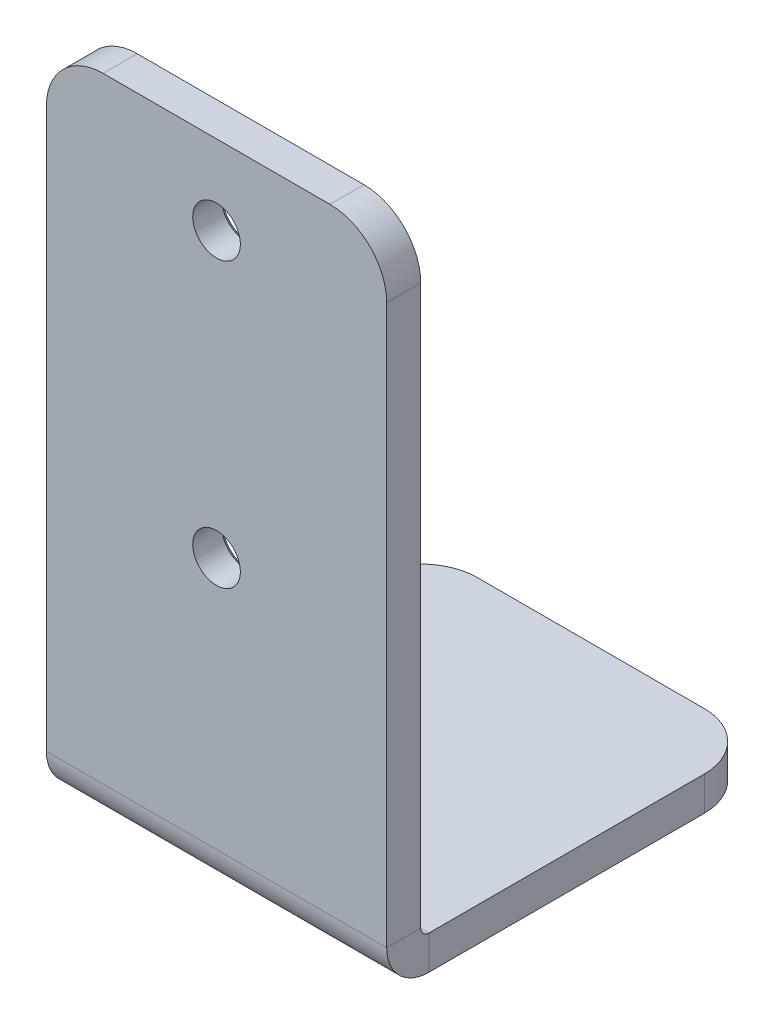
SolidWorks part; units mm, degrees
note: The reader was unsure of these and kept them because the rebuilt part matched: bend radius of "TabanBükümü1".
ref_plane "Ön Düzlem" through (0, 0, 0) normal (0, 0, 1) x (1, 0, 0)
ref_plane "Üst Düzlem" through (0, 0, 0) normal (0, 1, 0) x (1, 0, 0)
ref_plane "Sağ Düzlem" through (0, 0, 0) normal (1, 0, 0) x (0, 0, -1)
sketch "Sketch1" plane through (0, 0, 0) normal (1, 0, 0) x (0, 0, -1)
  line L0 (0, 0) -> (0, -55)
  line L1 (0, -55) -> (30, -55)
  dimension "D1" = 55
  dimension "D2" = 30
base flange "Base-Flange1" sketch "Sketch1" end condition mid plane depth 30 reverse direction no thickness 3 reverse thickness direction no bend radius 0.7366
bend "TabanBükümü1" bend radius 0.7366 bend angle 90 parameters "D5"=1
sketch "Sketch6" plane through (0, 0, 0) normal (0, 0, -1) x (-1, 0, 0)
  line L0 (0, -58) -> (0, -32) construction
  line L1 (-15, -58) -> (15, -58) construction
  line L2 (0, 0) -> (0, -55) construction
  line L3 (0, -32) -> (0, -7) construction
  dimension "D1" = 25
  dimension "D2" = 26
hole_wizard "M5 Tapped Hole1" positions "Sketch7" profile "Sketch8" tap size "M5" standard "ISO"
sketch "Sketch7" plane through (0, 0, 0) normal (0, 0, -1) x (-1, 0, 0)
  point P0 (0, -32)
  point P3 (0, -7)
sketch "Sketch8" plane through (0, -32, 0) normal (1, 0, 0) x (0, 1, 0)
  line L0 (0, 0) -> (0, 15.2618)
  line L1 (0, 15.2618) -> (2.1, 14)
  line L2 (2.1, 14) -> (2.1, 0.425)
  line L3 (2.1, 0.425) -> (2.525, 0)
  line L5 (2.525, 0) -> (0, 0)
  line L6 (-2.1, 0.425) -> (-2.525, 0) construction
  line L10 (0, 15.2618) -> (-2.1, 14) construction
  line L11 (0, -6.35) -> (0, 107.95) construction
  dimension "Tap Drill Dia." = 4.2
  dimension "Tap Drill Depth" = 14
  dimension "Near C'Sink Dia." = 5.05
  dimension "Near C'Sink Angle" = 90
  dimension "Drill Angle" = 118
cosmetic thread "Hole Thread1"
cosmetic thread "Hole Thread2"
fillet "Fillet1" radius 5 4 edges at (-15, -56.5, -30) (15, -56.5, -30) (15, 0, 1.5) (-15, 0, 1.5)
sketch "Büküm-Çizgileri1" [suppressed] plane through (0, 0, 0) normal (0, 1, 0) x (1, 0, 0)
sketch "Sınırlandırma-Kutusu1" [suppressed] plane through (0, 0, 0) normal (0, 1, 0) x (1, 0, 0)
sheet metal parameters "Sac-Levha1" thickness 3 parameters "D1"=0.7366
flat pattern "Düz-Çoğaltma1" [suppressed]
sketch "Büküm-Çizgileri2" plane through (0, 0, 0) normal (0, 0, -1) x (-1, 0, 0)
  line L0 (15, -56.02) -> (-15, -56.02) construction
  line L1 (15, -56.02) -> (-15, -56.02) construction
sketch3d "Sınırlandırma-Kutusu2" [suppressed]
  line L0 (0, 0, 0) -> (0, -87.04, 0) construction
  line L1 (30, 0, 0) -> (30, -87.04, 0) construction
  line L2 (0, 0, 0) -> (30, 0, 0) construction
  line L3 (0, -87.04, 0) -> (30, -87.04, 0) construction
bend of the flat pattern "Düzleştirme TipiTabanBükümü1>1"
sheet metal parameters "Sac-Levha2" thickness 3 parameters "D1"=0.7366
flat pattern "Düz-Çoğaltma1"
sketch "Büküm-Çizgileri2" plane through (0, 0, 0) normal (0, 0, -1) x (-1, 0, 0)
  line L0 (15, -56.02) -> (-15, -56.02) construction
  line L1 (15, -56.02) -> (-15, -56.02) construction
sketch3d "Sınırlandırma-Kutusu2" [suppressed]
  line L0 (0, -87.04, 0) -> (0, 0, 0) construction
  line L1 (30, -87.04, 0) -> (30, 0, 0) construction
  line L2 (0, -87.04, 0) -> (30, -87.04, 0) construction
  line L3 (0, 0, 0) -> (30, 0, 0) construction
bend of the flat pattern "Düzleştirme TipiTabanBükümü1>1"
